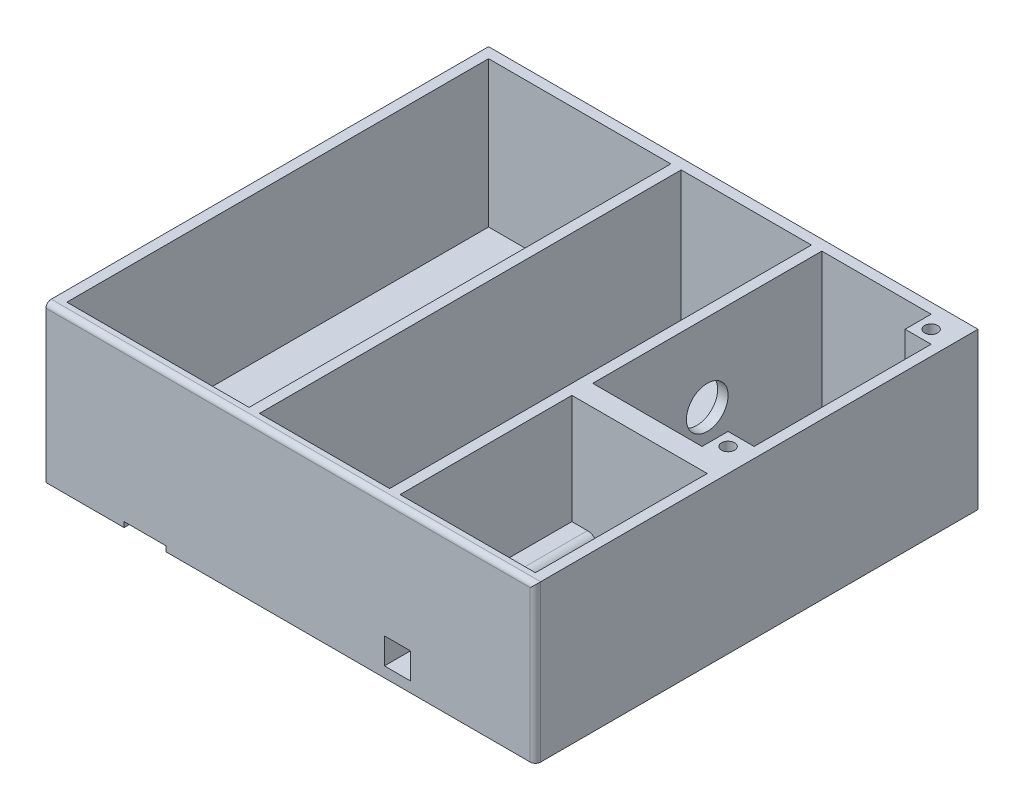
SolidWorks part; units mm, degrees
ref_plane "Front Plane" through (0, 0, 0) normal (0, 0, 1) x (1, 0, 0)
ref_plane "Top Plane" through (0, 0, 0) normal (0, 1, 0) x (1, 0, 0)
ref_plane "Right Plane" through (0, 0, 0) normal (1, 0, 0) x (0, 0, -1)
sketch "Sketch1" plane through (0, 0, 0) normal (0, 1, 0) x (1, 0, 0)
  line L1 (-47, 42.5) -> (47, 42.5)
  line L2 (-47, 42.5) -> (-47, -42.5)
  line L3 (-47, -42.5) -> (47, -42.5)
  line L4 (47, 42.5) -> (47, -42.5)
  line L5 (-47, 42.5) -> (47, -42.5) construction
  line L6 (-47, -42.5) -> (47, 42.5) construction
  point P0 (0, 0)
  dimension "D1" = 85
  dimension "D2" = 94
extrude "Boss-Extrude1" add sketch "Sketch1" along normal blind 30
sketch "Sketch2" plane through (0, 30, 0) normal (0, 1, 0) x (1, 0, 0)
  line L0 (-47, 42.5) -> (-47, -42.5) construction
  line L1 (-45, 40.5) -> (-10, 40.5)
  line L2 (-45, 40.5) -> (-45, -40.5)
  line L3 (-45, -40.5) -> (-10, -40.5)
  line L4 (-10, 40.5) -> (-10, -40.5)
  line L5 (-45, 40.5) -> (-10, -40.5) construction
  line L6 (-45, -40.5) -> (-10, 40.5) construction
  line L7 (-47, -42.5) -> (47, -42.5) construction
  line L8 (47, 42.5) -> (-47, 42.5) construction
  line L9 (47, -42.5) -> (47, 42.5) construction
  line L11 (-8, 40.5) -> (17, 40.5)
  line L12 (-8, 40.5) -> (-8, -40.5)
  line L13 (-8, -40.5) -> (17, -40.5)
  line L14 (17, 40.5) -> (17, -40.5)
  line L15 (-8, 40.5) -> (17, -40.5) construction
  line L16 (-8, -40.5) -> (17, 40.5) construction
  line L17 (19, -7.5) -> (45, -7.5)
  line L18 (19, -7.5) -> (19, -40.5)
  line L19 (19, -40.5) -> (45, -40.5)
  line L20 (45, -7.5) -> (45, -40.5)
  line L21 (19, -7.5) -> (45, -40.5) construction
  line L22 (19, -40.5) -> (45, -7.5) construction
  line L23 (19, 40.5) -> (45, 40.5)
  line L24 (19, 40.5) -> (19, -3.5)
  line L25 (19, -3.5) -> (45, -3.5)
  line L26 (45, 40.5) -> (45, -3.5)
  line L27 (19, 40.5) -> (45, -3.5) construction
  line L28 (19, -3.5) -> (45, 40.5) construction
  point P0 (-27.5, 0)
  point P13 (4.5, 0)
  point P18 (32, -24)
  point P23 (32, 18.5)
  dimension "D1" = 2
  dimension "D2" = 2
  dimension "D3" = 2
  dimension "D4" = 35
  dimension "D5" = 57
  dimension "D6" = 2
  dimension "D7" = 2
  dimension "D8" = 2
  dimension "D9" = 25
  dimension "D10" = 30
  dimension "D11" = 2
  dimension "D12" = 2
  dimension "D13" = 2
  dimension "D14" = 50
  dimension "D15" = 4
  dimension "D16" = 2
  dimension "D17" = 2
  dimension "D18" = 2
  dimension "D19" = 44
extrude "Cut-Extrude1" cut sketch "Sketch2" against normal blind 28
sketch "Sketch3" plane through (0, 2, 0) normal (0, 1, 0) x (1, 0, 0)
  line L1 (-45, 40.5) -> (-45, -40.5) construction
  circle A0 centre (-30, -32.583) radius 0.5
  circle A1 centre (-26, -32.583) radius 0.5
  dimension "D1" = 1
  dimension "D2" = 1
  dimension "D3" = 4
  dimension "D4" = 15
extrude "Cut-Extrude2" cut sketch "Sketch3" against normal blind 28
sketch "Sketch4" plane through (0, 0, 0) normal (0, -1, 0) x (-1, 0, 0)
  line L0 (24, -30.583) -> (24, -42.5)
  line L1 (24, -30.583) -> (32, -30.583)
  line L2 (24, -42.5) -> (32, -42.5)
  line L3 (32, -30.583) -> (32, -42.5)
  line L4 (47, -42.5) -> (-47, -42.5) construction
  circle A0 centre (30, -32.583) radius 0.5 construction
  circle A1 centre (26, -32.583) radius 0.5 construction
  dimension "D1" = 2
  dimension "D2" = 2
  dimension "D3" = 2
extrude "Cut-Extrude3" cut sketch "Sketch4" against normal blind 1
sketch "Sketch5" plane through (19, 0, 0) normal (1, 0, 0) x (0, 0, -1)
  line L0 (40.5, 2) -> (40.5, 30) construction
  line L1 (-3.5, 2) -> (-3.5, 30) construction
  line L2 (40.5, 30) -> (-3.5, 30) construction
  circle A0 centre (18.5, 15) radius 4
  dimension "D2" = 22
  dimension "D4" = 8
  dimension "D1" = 22
  dimension "D3" = 15
extrude "Cut-Extrude4" cut sketch "Sketch5" against normal up to surface (2 mm away) up to face at (17, 16, 0)
sketch "Sketch6" plane through (0, 2, 0) normal (0, 1, 0) x (1, 0, 0)
  line L1 (45, 40.5) -> (40, 40.5)
  line L2 (45, 40.5) -> (45, 35.5)
  line L3 (45, 35.5) -> (40, 35.5)
  line L4 (40, 40.5) -> (40, 35.5)
  line L5 (45, -3.5) -> (40, -3.5)
  line L6 (45, -3.5) -> (45, 1.5)
  line L7 (45, 1.5) -> (40, 1.5)
  line L8 (40, -3.5) -> (40, 1.5)
  dimension "D1" = 5
  dimension "D2" = 5
  dimension "D3" = 5
  dimension "D4" = 5
extrude "Boss-Extrude3" add sketch "Sketch6" along normal blind 28
sketch "Sketch7" plane through (0, 30, 0) normal (0, 1, 0) x (1, 0, 0)
  line L0 (40, 40.5) -> (40, 35.5) construction
  line L1 (40, 35.5) -> (45, 35.5) construction
  line L2 (45, 1.5) -> (40, 1.5) construction
  line L3 (40, 1.5) -> (40, -3.5) construction
  circle A0 centre (42.5, 38) radius 1.25
  circle A1 centre (42.5, -1) radius 1.25
  point P8 (42.5, 1.5)
  dimension "D1" = 2.5
  dimension "D3" = 2.5
  dimension "D4" = 2.5
  dimension "D6" = 2.5
  dimension "D2" = 2.5
  dimension "D5" = 2.5
extrude "Cut-Extrude5" cut sketch "Sketch7" against normal blind 20
fillet "Fillet1" radius 1 2 edges at (0, 30, 42.5) (47, 15, 42.5)
sketch "Sketch9" plane through (0, 2, 0) normal (0, 1, 0) x (1, 0, 0)
  line L0 (19, -40.5) -> (45, -40.5) construction
  line L1 (19, -7.5) -> (24, -7.5)
  line L2 (19, -7.5) -> (19, -40.5)
  line L3 (19, -40.5) -> (24, -40.5)
  line L4 (24, -7.5) -> (24, -40.5)
  dimension "D1" = 5
extrude "Boss-Extrude4" add sketch "Sketch9" along normal blind 7
sketch "Sketch10" plane through (0, 0, 42.5) normal (0, 0, 1) x (1, 0, 0)
  line L0 (-24, 0) -> (46, 0) construction
  line L1 (18, 7) -> (23, 7)
  line L2 (18, 7) -> (18, 2)
  line L3 (18, 2) -> (23, 2)
  line L4 (23, 7) -> (23, 2)
  line L5 (-47, 29) -> (-47, 0) construction
  dimension "D1" = 5
  dimension "D2" = 5
  dimension "D3" = 2
  dimension "D4" = 65
extrude "Cut-Extrude7" cut sketch "Sketch10" against normal up to surface (39 mm away) up to face at (29.5, 16, 3.5)
fillet "Fillet3" radius 2 1 edges at (24, 9, 24)
